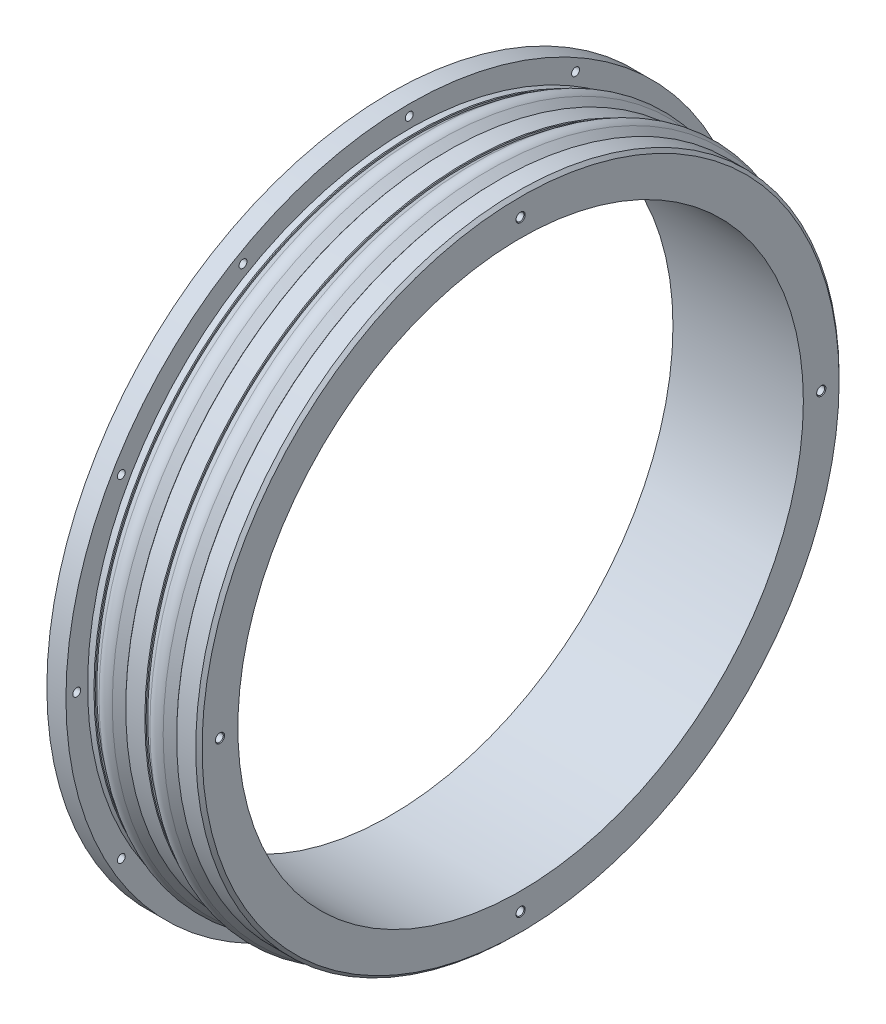
SolidWorks part; units mm, degrees
material "6061 Alloy"
ref_plane "Front Plane" through (0, 0, 0) normal (0, 0, 1) x (1, 0, 0)
ref_plane "Top Plane" through (0, 0, 0) normal (0, 1, 0) x (1, 0, 0)
ref_plane "Right Plane" through (0, 0, 0) normal (1, 0, 0) x (0, 0, -1)
sketch "Sketch2" plane through (0, 0, 0) normal (0, 1, 0) x (1, 0, 0)
  line L0 (0, 0) -> (0, 88.9) construction
  line L1 (0, 88.9) -> (41, 88.9)
  line L2 (41, 88.9) -> (41, 101.15)
  line L3 (41, 101.15) -> (33.8, 101.15)
  line L4 (33.8, 101.15) -> (33.8, 100.15) construction
  line L5 (33.8, 100.15) -> (24.2, 100.15) construction
  line L6 (24.2, 100.15) -> (24.2, 101.15) construction
  line L7 (24.2, 101.15) -> (8.2, 101.15) construction
  line L8 (8.2, 101.15) -> (8.2, 100.15) construction
  line L9 (8.2, 100.15) -> (17.8, 100.15) construction
  line L10 (17.8, 100.15) -> (17.8, 101.15) construction
  line L11 (17.8, 101.15) -> (6, 101.15) construction
  line L12 (6, 101.15) -> (6, 107.95)
  line L13 (6, 107.95) -> (0, 107.95)
  line L14 (0, 107.95) -> (0, 101.27)
  line L15 (0, 101.27) -> (0.75, 101.27)
  line L16 (0.75, 101.27) -> (0.75, 98.171) construction
  line L17 (0.75, 98.171) -> (0, 98.171)
  line L18 (0, 98.171) -> (0, 88.9)
  line L19 (6, 101.4) -> (41, 101.4) construction
  line L20 (6, 101.62) -> (41, 101.62) construction
  line L21 (8.2, 100.45) -> (10.9167, 102.4624)
  line L22 (0, 0) -> (-153832.3837, 0) construction
  line L23 (13, 100.45) -> (13, 100.15) construction
  line L24 (6, 101.15) -> (8.2, 101.15)
  line L25 (17.8, 101.15) -> (24.2, 101.15)
  line L26 (15.0833, 102.4624) -> (17.8, 100.45)
  line L27 (24.2, 100.45) -> (26.9167, 102.4624)
  line L28 (29, 100.45) -> (29, 100.15) construction
  line L29 (31.0833, 102.4624) -> (33.8, 100.45)
  line L30 (0.0113, 100.7289) -> (0.75, 101.27)
  line L31 (0.0113, 98.7121) -> (0.75, 98.171)
  line L32 (8.2, 101.15) -> (8.2, 100.45)
  line L33 (17.8, 100.45) -> (17.8, 101.15)
  line L34 (24.2, 101.15) -> (24.2, 100.45)
  line L35 (33.8, 100.45) -> (33.8, 101.15)
  line L36 (8.2, 100.45) -> (17.8, 100.45) construction
  line L37 (24.2, 100.45) -> (33.8, 100.45) construction
  line L38 (41, 96.15) -> (0, 96.15) construction
  arc A0 (0.0113, 100.7289) -> (0.0113, 98.7121) centre (0.75, 99.7205) ccw
  arc A1 (10.9167, 102.4624) -> (15.0833, 102.4624) centre (13, 99.65) cw
  arc A2 (26.9167, 102.4624) -> (31.0833, 102.4624) centre (29, 99.65) cw
  dimension "D3" = 1.25
  dimension "D8" = 12
  dimension "D9" = 16
  dimension "D18" = 3.5
  dimension "D1" = 202.8
  dimension "D2" = 203.24
  dimension "D4" = 35
  dimension "D5" = 1
  dimension "D6" = 0.25
  dimension "D7" = 202.3
  dimension "D10" = 196.342
  dimension "D11" = 177.8
  dimension "D12" = 215.9
  dimension "D13" = 6
  dimension "D14" = 9.6
  dimension "D15" = 0.75
  dimension "D16" = 3.099
  dimension "D17" = 0.3
  dimension "D19" = 5
revolve "Revolve1" add sketch "Sketch2" angle 360 about L22 region at (19.2337, 0, -95.9457)
chamfer "Chamfer1" distance 1 angle 45 1 edges at (41, 0, -101.15)
chamfer "Chamfer2" distance 0.2 angle 45 6 edges at (0, 0, -98.171) (0, 0, -101.27) (33.8, 0, -101.15) (24.2, 0, -101.15) (17.8, 0, -101.15) (8.2, 0, -101.15)
sketch "Sketch3" plane through (6, 0, 0) normal (1, 0, 0) x (0, 0, -1)
  line L0 (0, 101.15) -> (0, 107.95) construction
  line L1 (0, -101.15) -> (0, -107.95) construction
  circle A1 centre (0, 0) radius 101.15 construction
  circle A2 centre (0, 0) radius 107.95 construction
  point P9 (0, 104.55)
  point P21 (0, 0)
  point P22 (52.275, 90.543)
  point P23 (90.543, 52.275)
  point P24 (104.55, 0)
  point P25 (90.543, -52.275)
  point P26 (52.275, -90.543)
  point P27 (0, -104.55)
  point P28 (-52.275, -90.543)
  point P29 (-90.543, -52.275)
  point P30 (-104.55, 0)
  point P31 (-90.543, 52.275)
  point P32 (-52.275, 90.543)
  point P33 (0, 0)
  dimension "D1" = 12
hole_wizard "Tap Drill for M3x0.5 Tap2" positions "3DSketch2" profile "Sketch6" hole size "M3x0.5" standard "ANSI Metric" end condition through all
sketch3d "3DSketch2"
  point P0 (6, 104.55, 0)
  point P3 (6, 90.543, -52.275)
  point P6 (6, 52.275, -90.543)
  point P9 (6, 0, -104.55)
  point P12 (6, -52.275, -90.543)
  point P15 (6, -90.543, -52.275)
  point P18 (6, -104.55, 0)
  point P21 (6, -90.543, 52.275)
  point P24 (6, -52.275, 90.543)
  point P27 (6, 0, 104.55)
  point P30 (6, 52.275, 90.543)
  point P33 (6, 90.543, 52.275)
sketch "Sketch6" plane through (6, 104.55, 0) normal (0, 1, 0) x (0, 0, -1)
  line L0 (0, 0) -> (0, 6.5)
  line L1 (0, 6.5) -> (1.25, 6.5)
  line L2 (1.25, 6.5) -> (1.25, 0)
  line L5 (1.25, 0) -> (0, 0)
  line L11 (0, -6.35) -> (0, 107.95) construction
  dimension "Thru Hole Dia." = 2.5
  dimension "Thru Hole Depth" = 6.5
sketch "Sketch7" plane through (41, 0, 0) normal (1, 0, 0) x (0, 0, -1)
  line L0 (0, 100.15) -> (0, 88.9) construction
  line L1 (0, -100.15) -> (0, -88.9) construction
  circle A0 centre (0, 0) radius 100.15 construction
  circle A1 centre (0, 0) radius 88.9 construction
  point P7 (0, 94.525)
  point P11 (94.525, 0)
  point P12 (0, -94.525)
  point P13 (-94.525, 0)
  point P14 (0, 0)
  dimension "D1" = 4
hole_wizard "Tap Drill for M3x0.5 Tap3" positions "3DSketch3" profile "Sketch8" hole size "M3x0.5" standard "ANSI Metric"
sketch3d "3DSketch3"
  point P0 (41, 94.525, 0)
  point P3 (41, 0, -94.525)
  point P6 (41, -94.525, 0)
  point P9 (41, 0, 94.525)
sketch "Sketch8" plane through (41, 94.525, 0) normal (0, 1, 0) x (0, 0, -1)
  line L0 (0, 0) -> (0, 4.7511)
  line L1 (0, 4.7511) -> (1.25, 4)
  line L2 (1.25, 4) -> (1.25, 0)
  line L5 (1.25, 0) -> (0, 0)
  line L10 (0, 4.7511) -> (-1.25, 4) construction
  line L11 (0, -6.35) -> (0, 107.95) construction
  dimension "Hole Dia." = 2.5
  dimension "Hole Depth" = 4
  dimension "Drill Angle" = 118
chamfer "Chamfer3" distance 0.2 angle 45 4 edges at (41, 0, 93.275) (41, -94.525, -1.25) (41, 0, -95.775) (41, 94.525, -1.25)
chamfer "Chamfer4" distance 0.2 angle 45 12 edges at (0, -52.275, -89.293) (0, -90.543, -51.025) (0, -104.55, 1.25) (0, -90.543, 53.525) (0, -52.275, 91.793) (0, 0, 105.8) (0, 52.275, 91.793) (0, 90.543, 53.525) (0, 104.55, 1.25) (0, 90.543, -51.025) (0, 52.275, -89.293) (0, 0, -103.3)
